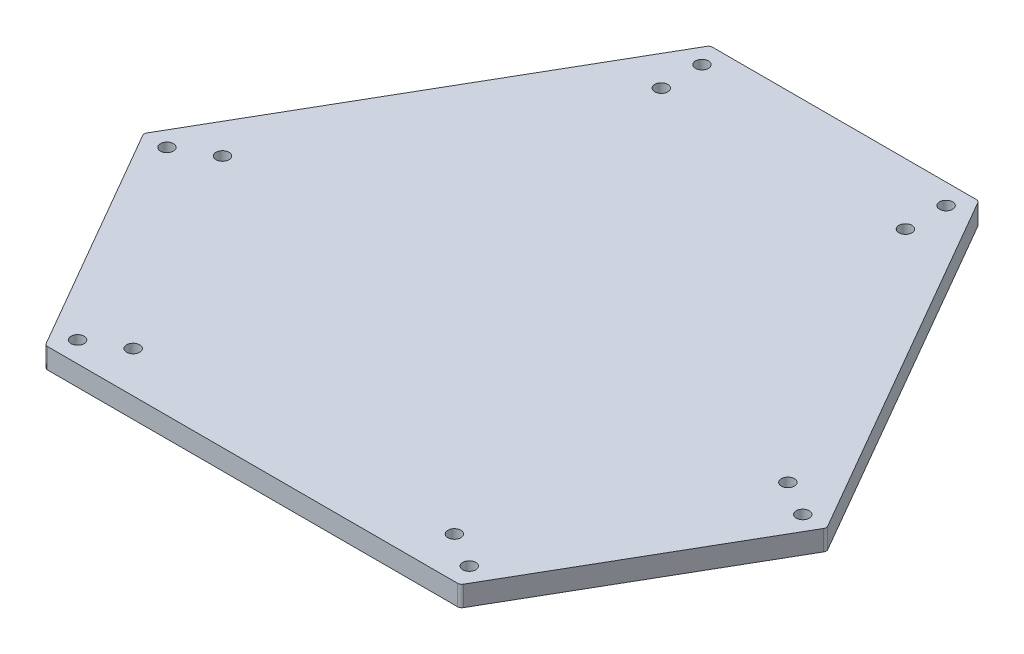
SolidWorks part; units mm, degrees
ref_plane "正面" through (0, 0, 0) normal (0, 0, 1) x (1, 0, 0)
ref_plane "平面" through (0, 0, 0) normal (0, 1, 0) x (1, 0, 0)
ref_plane "右側面" through (0, 0, 0) normal (1, 0, 0) x (0, 0, -1)
sketch "ｽｹｯﾁ1" plane through (0, 0, 0) normal (0, 1, 0) x (1, 0, 0)
  line L0 (53.9634, -62.3327) -> (50.9634, -67.5288) construction
  line L1 (50.9634, -67.5288) -> (51.8294, -68.0288) construction
  line L2 (51.8294, -68.0288) -> (54.8294, -62.8327) construction
  line L3 (54.8294, -62.8327) -> (53.9634, -62.3327) construction
  line L4 (-50.9634, -67.5288) -> (50.9634, -67.5288) construction
  line L5 (53.9634, -62.3327) -> (80.9634, -15.5673) construction
  line L6 (83.9634, -10.3712) -> (80.9634, -15.5673) construction
  line L7 (84.8294, -10.8712) -> (83.9634, -10.3712) construction
  line L8 (81.8294, -16.0673) -> (84.8294, -10.8712) construction
  line L9 (80.9634, -15.5673) -> (81.8294, -16.0673) construction
  line L10 (33, 77.9) -> (83.9634, -10.3712) construction
  line L11 (-50.9634, -67.5288) -> (-53.9634, -62.3327) construction
  line L12 (-51.8294, -68.0288) -> (-50.9634, -67.5288) construction
  line L13 (-54.8294, -62.8327) -> (-51.8294, -68.0288) construction
  line L14 (-53.9634, -62.3327) -> (-54.8294, -62.8327) construction
  line L15 (-80.9634, -15.5673) -> (-53.9634, -62.3327) construction
  line L16 (-80.9634, -15.5673) -> (-83.9634, -10.3712) construction
  line L17 (-83.9634, -10.3712) -> (-84.8294, -10.8712) construction
  line L18 (-84.8294, -10.8712) -> (-81.8294, -16.0673) construction
  line L19 (-81.8294, -16.0673) -> (-80.9634, -15.5673) construction
  line L20 (-83.9634, -10.3712) -> (-33, 77.9) construction
  line L21 (-33, 77.9) -> (-27, 77.9) construction
  line L22 (-27, 77.9) -> (-27, 78.9) construction
  line L23 (-27, 78.9) -> (-33, 78.9) construction
  line L24 (-33, 78.9) -> (-33, 77.9) construction
  line L25 (-27, 77.9) -> (27, 77.9) construction
  line L26 (27, 77.9) -> (33, 77.9) construction
  line L27 (27, 78.9) -> (27, 77.9) construction
  line L28 (33, 78.9) -> (27, 78.9) construction
  line L29 (33, 77.9) -> (33, 78.9) construction
  line L30 (52.4324, -61.4488) -> (35.3438, -51.5827) construction
  line L31 (35.3438, -51.5827) -> (32.3438, -56.7788) construction
  line L32 (32.3438, -56.7788) -> (49.4324, -66.645) construction
  line L33 (49.4324, -66.645) -> (52.4324, -61.4488) construction
  line L34 (82.4324, -9.4873) -> (65.3438, 0.3788) construction
  line L35 (65.3438, 0.3788) -> (62.3438, -4.8173) construction
  line L36 (62.3438, -4.8173) -> (79.4324, -14.6834) construction
  line L37 (79.4324, -14.6834) -> (82.4324, -9.4873) construction
  line L38 (-49.4324, -66.645) -> (-32.3438, -56.7788) construction
  line L39 (-32.3438, -56.7788) -> (-35.3438, -51.5827) construction
  line L40 (-35.3438, -51.5827) -> (-52.4324, -61.4488) construction
  line L41 (-52.4324, -61.4488) -> (-49.4324, -66.645) construction
  line L42 (27, 76.1322) -> (27, 56.4) construction
  line L43 (27, 56.4) -> (33, 56.4) construction
  line L44 (33, 56.4) -> (33, 76.1322) construction
  line L45 (33, 76.1322) -> (27, 76.1322) construction
  line L46 (-33, 56.4) -> (-27, 56.4) construction
  line L47 (-27, 56.4) -> (-27, 76.1322) construction
  line L48 (-27, 76.1322) -> (-33, 76.1322) construction
  line L49 (-33, 76.1322) -> (-33, 56.4) construction
  line L50 (-65.3438, 0.3788) -> (-82.4324, -9.4873) construction
  line L51 (-62.3438, -4.8173) -> (-65.3438, 0.3788) construction
  line L52 (-79.4324, -14.6834) -> (-62.3438, -4.8173) construction
  line L53 (-82.4324, -9.4873) -> (-79.4324, -14.6834) construction
  line L54 (53.9634, -62.3327) -> (50.9634, -67.5288)
  line L55 (50.9634, -67.5288) -> (51.8294, -68.0288)
  line L56 (51.8294, -68.0288) -> (54.8294, -62.8327)
  line L57 (54.8294, -62.8327) -> (53.9634, -62.3327)
  line L58 (-50.9634, -67.5288) -> (50.9634, -67.5288)
  line L59 (53.9634, -62.3327) -> (80.9634, -15.5673)
  line L60 (83.9634, -10.3712) -> (80.9634, -15.5673)
  line L61 (84.8294, -10.8712) -> (83.9634, -10.3712)
  line L62 (81.8294, -16.0673) -> (84.8294, -10.8712)
  line L63 (80.9634, -15.5673) -> (81.8294, -16.0673)
  line L64 (33, 77.9) -> (83.9634, -10.3712)
  line L65 (-50.9634, -67.5288) -> (-53.9634, -62.3327)
  line L66 (-51.8294, -68.0288) -> (-50.9634, -67.5288)
  line L67 (-54.8294, -62.8327) -> (-51.8294, -68.0288)
  line L68 (-53.9634, -62.3327) -> (-54.8294, -62.8327)
  line L69 (-80.9634, -15.5673) -> (-53.9634, -62.3327)
  line L70 (-80.9634, -15.5673) -> (-83.9634, -10.3712)
  line L71 (-83.9634, -10.3712) -> (-84.8294, -10.8712)
  line L72 (-84.8294, -10.8712) -> (-81.8294, -16.0673)
  line L73 (-81.8294, -16.0673) -> (-80.9634, -15.5673)
  line L74 (-83.9634, -10.3712) -> (-33, 77.9)
  line L75 (-33, 77.9) -> (-27, 77.9)
  line L76 (-27, 77.9) -> (-27, 78.9)
  line L77 (-27, 78.9) -> (-33, 78.9)
  line L78 (-33, 78.9) -> (-33, 77.9)
  line L79 (-27, 77.9) -> (27, 77.9)
  line L80 (27, 77.9) -> (33, 77.9)
  line L81 (27, 78.9) -> (27, 77.9)
  line L82 (33, 78.9) -> (27, 78.9)
  line L83 (33, 77.9) -> (33, 78.9)
  line L84 (52.4324, -61.4488) -> (35.3438, -51.5827)
  line L85 (35.3438, -51.5827) -> (32.3438, -56.7788)
  line L86 (32.3438, -56.7788) -> (49.4324, -66.645)
  line L87 (49.4324, -66.645) -> (52.4324, -61.4488)
  line L88 (82.4324, -9.4873) -> (65.3438, 0.3788)
  line L89 (65.3438, 0.3788) -> (62.3438, -4.8173)
  line L90 (62.3438, -4.8173) -> (79.4324, -14.6834)
  line L91 (79.4324, -14.6834) -> (82.4324, -9.4873)
  line L92 (-49.4324, -66.645) -> (-32.3438, -56.7788)
  line L93 (-32.3438, -56.7788) -> (-35.3438, -51.5827)
  line L94 (-35.3438, -51.5827) -> (-52.4324, -61.4488)
  line L95 (-52.4324, -61.4488) -> (-49.4324, -66.645)
  line L96 (27, 76.1322) -> (27, 56.4)
  line L97 (27, 56.4) -> (33, 56.4)
  line L98 (33, 56.4) -> (33, 76.1322)
  line L99 (33, 76.1322) -> (27, 76.1322)
  line L100 (-33, 56.4) -> (-27, 56.4)
  line L101 (-27, 56.4) -> (-27, 76.1322)
  line L102 (-27, 76.1322) -> (-33, 76.1322)
  line L103 (-33, 76.1322) -> (-33, 56.4)
  line L104 (-65.3438, 0.3788) -> (-82.4324, -9.4873)
  line L105 (-62.3438, -4.8173) -> (-65.3438, 0.3788)
  line L106 (-79.4324, -14.6834) -> (-62.3438, -4.8173)
  line L107 (-82.4324, -9.4873) -> (-79.4324, -14.6834)
sketch "ｽｹｯﾁ2" plane through (0, 0, 0) normal (0, 1, 0) x (1, 0, 0)
  line L0 (-83.9634, -10.3712) -> (-50.9634, -67.5288)
  line L1 (-50.9634, -67.5288) -> (50.9634, -67.5288)
  line L2 (50.9634, -67.5288) -> (83.9634, -10.3712)
  line L3 (83.9634, -10.3712) -> (33, 77.9)
  line L4 (33, 77.9) -> (-33, 77.9)
  line L5 (-33, 77.9) -> (-83.9634, -10.3712)
  circle A0 centre (0, 0) radius 84.6015 construction
  point P6 (0, 77.9)
  point P11 (83.9634, -10.3712)
  dimension "D1" = 66
extrude "ﾎﾞｽ - 押し出し1" add sketch "ｽｹｯﾁ2" along normal mid plane 5
fillet "ﾌｨﾚｯﾄ1" radius 1 6 edges at (-33, 0, -77.9) (33, 0, -77.9) (83.9634, 0, 10.3712) (50.9634, 0, 67.5288) (-83.9634, 0, 10.3712) (-50.9634, 0, 67.5288)
sketch "ｽｹｯﾁ3" plane through (0, 2.5, 0) normal (0, 1, 0) x (1, 0, 0)
  line L0 (-30, 77.9) -> (-30, 72.9) construction
  line L1 (-33, 77.9) -> (-27, 77.9) construction
  line L2 (-30, 72.9) -> (-30, 62.9) construction
  line L3 (0, 0) -> (0, 77.9) construction
  line L4 (-27, 77.9) -> (27, 77.9) construction
  line L5 (30, 72.9) -> (30, 62.9) construction
  line L6 (30, 77.9) -> (30, 72.9) construction
  circle A0 centre (-30, 72.9) radius 1.6
  circle A1 centre (-30, 62.9) radius 1.6
  circle A2 centre (30, 62.9) radius 1.6
  circle A3 centre (30, 72.9) radius 1.6
  dimension "D3" = 3.2
  dimension "D4" = 3.2
  dimension "D1" = 5
  dimension "D2" = 10
extrude "ｶｯﾄ - 押し出し1" cut sketch "ｽｹｯﾁ3" against normal through all both and the other way through all
ref_axis "軸1" through (0, 2.75, 0) along (0, -1, 0)
pattern_circular "円形ﾊﾟﾀｰﾝ1" count 3 over 360 about axis through (0, 2.75, 0) along (0, -1, 0) of "ｶｯﾄ - 押し出し1"
